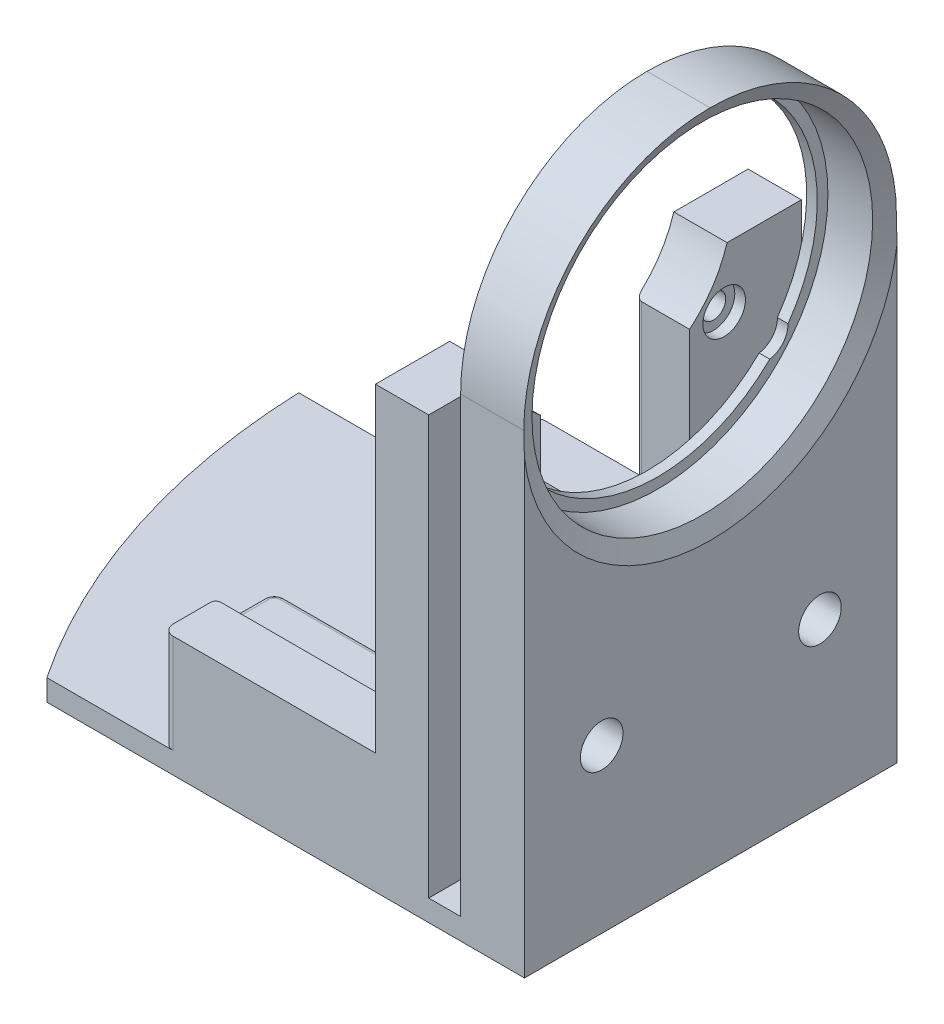
SolidWorks part; units mm, degrees
ref_plane "정면" through (0, 0, 0) normal (0, 0, 1) x (1, 0, 0)
ref_plane "윗면" through (0, 0, 0) normal (0, 1, 0) x (1, 0, 0)
ref_plane "우측면" through (0, 0, 0) normal (1, 0, 0) x (0, 0, -1)
sketch "스케치1" plane through (0, 0, 0) normal (0, 1, 0) x (1, 0, 0)
  line L1 (-11.2427, -2.5271) -> (-67.4527, -2.5271)
  line L2 (-11.2427, -2.5271) -> (-11.2427, -66.5571)
  arc A0 (-67.4527, -2.5271) -> (-11.2427, -66.5571) centre (0, 0) ccw
  dimension "D1" = 135
  dimension "D2" = 56.21
  dimension "D3" = 64.03
extrude "보스-돌출1" add sketch "스케치1" along normal blind 2 contours L1 A0 L2 region at (-34.5712, 0, 28.7061)
sketch "스케치2" plane through (0, 2, 0) normal (0, 1, 0) x (1, 0, 0)
  line L1 (-11.2427, -2.5271) -> (-17.2427, -2.5271)
  line L2 (-11.2427, -2.5271) -> (-11.2427, -37.5271)
  line L3 (-11.2427, -37.5271) -> (-17.2427, -37.5271)
  line L4 (-17.2427, -2.5271) -> (-17.2427, -37.5271)
  dimension "D1" = 35
  dimension "D2" = 6
extrude "보스-돌출2" add sketch "스케치2" along normal blind 60
fillet "필렛1" radius 17.5 2 edges at (-14.2427, 62, 2.5271) (-14.2427, 62, 37.5271)
sketch "스케치3" plane through (-11.2427, 0, 0) normal (1, 0, 0) x (0, 0, -1)
  circle A0 centre (-20.0271, 44.5) radius 16
  dimension "D1" = 32
extrude "컷-돌출1" cut sketch "스케치3" against normal blind 5
chamfer "모따기1" distance 0.8 angle 64 1 edges at (-11.2427, 44.5, 4.0271) first distance on face at (-16.2427, 44.5, 4.0271)
sketch "스케치4" plane through (-16.2427, 0, 0) normal (1, 0, 0) x (0, 0, -1)
  circle A0 centre (-20.0271, 44.5) radius 15
  circle A1 centre (-20.0271, 44.5) radius 16 construction
  dimension "D1" = 1
extrude "컷-돌출2" cut sketch "스케치4" against normal through all
sketch "스케치5" plane through (0, 2, 0) normal (0, 1, 0) x (1, 0, 0)
  line L0 (-17.2427, -2.5271) -> (-67.4527, -2.5271) construction
  line L1 (-20.2427, -2.5271) -> (-45.2427, -2.5271)
  line L2 (-20.2427, -2.5271) -> (-20.2427, -13.0271)
  line L3 (-20.2427, -13.0271) -> (-45.2427, -13.0271)
  line L4 (-45.2427, -2.5271) -> (-45.2427, -13.0271)
  line L5 (-17.2427, -2.5271) -> (-17.2427, -37.5271) construction
  line L6 (-20.2427, -27.0271) -> (-45.2427, -27.0271)
  line L7 (-20.2427, -27.0271) -> (-20.2427, -37.5271)
  line L8 (-20.2427, -37.5271) -> (-45.2427, -37.5271)
  line L9 (-45.2427, -27.0271) -> (-45.2427, -37.5271)
  dimension "D1" = 10.5
  dimension "D2" = 25
  dimension "D3" = 35
  dimension "D4" = 3
extrude "보스-돌출3" add sketch "스케치5" along normal blind 7.3
sketch "스케치6" plane through (0, 9.3, 0) normal (0, 1, 0) x (1, 0, 0)
  line L0 (-45.2427, -32.5271) -> (-25.2427, -32.5271)
  line L1 (-45.2427, -2.5271) -> (-20.2427, -2.5271)
  line L2 (-45.2427, -2.5271) -> (-45.2427, -7.5271)
  line L3 (-25.2427, -13.0271) -> (-20.2427, -13.0271)
  line L4 (-20.2427, -2.5271) -> (-20.2427, -13.0271)
  line L5 (-45.2427, -37.5271) -> (-20.2427, -37.5271)
  line L6 (-45.2427, -37.5271) -> (-45.2427, -32.5271)
  line L7 (-25.2427, -27.0271) -> (-20.2427, -27.0271)
  line L8 (-20.2427, -37.5271) -> (-20.2427, -27.0271)
  line L9 (-45.2427, -7.5271) -> (-25.2427, -7.5271)
  line L10 (-25.2427, -7.5271) -> (-25.2427, -13.0271)
  line L11 (-25.2427, -32.5271) -> (-25.2427, -27.0271)
  line L12 (-45.2427, -13.0271) -> (-20.2427, -13.0271) construction
  line L13 (-45.2427, -27.0271) -> (-20.2427, -27.0271) construction
  line L14 (-25.2427, -37.5271) -> (-25.2427, -27.0271) construction
  line L15 (-45.2427, -32.5271) -> (-20.2427, -32.5271) construction
  line L16 (-25.2427, -2.5271) -> (-25.2427, -13.0271) construction
  line L17 (-45.2427, -7.5271) -> (-20.2427, -7.5271) construction
  dimension "D1" = 5.5
  dimension "D2" = 5.5
  dimension "D3" = 5
  dimension "D4" = 5
extrude "보스-돌출4" add sketch "스케치6" along normal blind 2
fillet "필렛2" radius 1 4 edges at (-45.2427, 6.65, 37.5271) (-45.2427, 5.65, 27.0271) (-45.2427, 5.65, 13.0271) (-45.2427, 6.65, 2.5271)
sketch "스케치7" plane through (-25.2427, 0, 0) normal (-1, 0, 0) x (0, 0, 1)
  line L0 (13.0271, 9.3) -> (13.0271, 2) construction
  line L1 (2.5271, 11.3) -> (13.0271, 11.3)
  line L2 (2.5271, 11.3) -> (2.5271, 41.3)
  line L3 (2.5271, 41.3) -> (9.5029, 41.3)
  line L4 (13.0271, 11.3) -> (13.0271, 36.0147)
  line L5 (37.5271, 11.3) -> (27.0271, 11.3)
  line L6 (37.5271, 11.3) -> (37.5271, 41.3)
  line L7 (37.5271, 41.3) -> (30.5514, 41.3)
  line L8 (27.0271, 11.3) -> (27.0271, 36.0147)
  arc A0 (27.0271, 36.0147) -> (30.5514, 41.3) centre (20.0271, 44.5) ccw
  arc A1 (9.5029, 41.3) -> (13.0271, 36.0147) centre (20.0271, 44.5) ccw
  dimension "D2" = 22
  dimension "D1" = 30
extrude "보스-돌출5" add sketch "스케치7" against normal blind 5
sketch "스케치9" plane through (-25.2427, 0, 0) normal (-1, 0, 0) x (0, 0, 1)
  line L0 (7.5271, 9.3) -> (13.0271, 9.3) construction
  line L1 (9.7771, 35.8) -> (30.2771, 35.8) construction
  line L2 (9.7771, 35.8) -> (9.7771, 15.3) construction
  line L3 (9.7771, 15.3) -> (30.2771, 15.3) construction
  line L4 (30.2771, 35.8) -> (30.2771, 15.3) construction
  circle A0 centre (20.0271, 44.5) radius 15 construction
  circle A1 centre (9.7771, 35.8) radius 1.15
  circle A2 centre (9.7771, 15.3) radius 1.15
  circle A3 centre (30.2771, 15.3) radius 1.15
  circle A4 centre (30.2771, 35.8) radius 1.15
  dimension "D4" = 10.25
  dimension "D5" = 2.3
  dimension "D1" = 20.5
  dimension "D2" = 20.5
  dimension "D3" = 6
extrude "컷-돌출3" cut sketch "스케치9" against normal through all
sketch "스케치10" plane through (-11.2427, 0, 0) normal (1, 0, 0) x (0, 0, -1)
  circle A0 centre (-30.2771, 15.3) radius 2
  circle A1 centre (-9.7771, 15.3) radius 2
  circle A2 centre (-9.7771, 35.8) radius 2
  circle A3 centre (-30.2771, 35.8) radius 2
  dimension "D1" = 4
extrude "컷-돌출4" cut sketch "스케치10" against normal blind 10
fillet "필렛3" radius 0.5 12 edges at (-45.2427, 10.3, 7.5271) (-45.2427, 10.3, 32.5271) (-34.7427, 9.3, 13.0271) (-44.9498, 9.3, 12.7342) (-34.7427, 9.3, 27.0271) (-44.9498, 9.3, 27.32) (-45.2427, 9.3, 9.7771) (-45.2427, 9.3, 30.2771) (-35.2427, 9.3, 32.5271) (-35.2427, 9.3, 7.5271) (-25.2427, 22.6574, 27.0271) (-25.2427, 22.6574, 13.0271)
sketch "스케치12" plane through (0, 2, 0) normal (0, 1, 0) x (1, 0, 0)
  line L0 (-11.2427, -37.5271) -> (-11.2427, -66.5571)
  line L1 (-11.2427, -66.5571) -> (-67.4527, -66.5571)
  line L2 (-67.4527, -66.5571) -> (-67.4527, -37.5271)
  line L3 (-67.4527, -37.5271) -> (-11.2427, -37.5271)
  point P4 (0, 0)
extrude "컷-돌출5" cut sketch "스케치12" against normal through all
